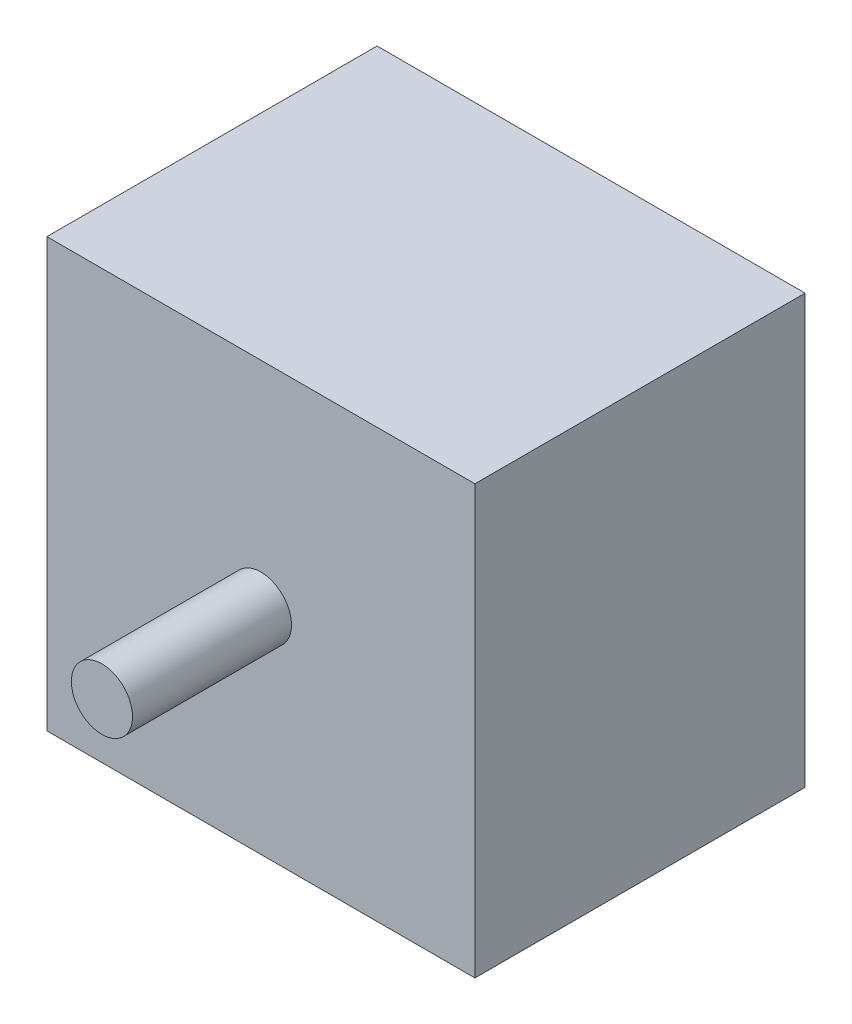
SolidWorks part; units mm, degrees
ref_plane "Front Plane" through (0, 0, 0) normal (0, 0, 1) x (1, 0, 0)
ref_plane "Top Plane" through (0, 0, 0) normal (0, 1, 0) x (1, 0, 0)
ref_plane "Right Plane" through (0, 0, 0) normal (1, 0, 0) x (0, 0, -1)
sketch "Sketch1" plane through (0, 0, 0) normal (0, 0, 1) x (1, 0, 0)
  line L0 (0, 17.5) -> (35, 17.5) construction
  line L1 (0, 0) -> (35, 0)
  line L2 (0, 0) -> (0, 35)
  line L3 (0, 35) -> (35, 35)
  line L4 (35, 0) -> (35, 35)
  line L5 (17.5, 0) -> (17.5, 35) construction
  line L6 (15.4391, 18.9151) -> (19.5609, 18.9151)
  circle A0 centre (17.5, 17.5) radius 2.5
  dimension "D3" = 5
  dimension "D1" = 35
  dimension "D2" = 35
extrude "Boss-Extrude1" add sketch "Sketch1" along normal blind 27 contours L1 L4 L3 L2 A0 | L6 A0 | L6 A0 region at (0.495, 17.5, 0) region at (17.5, 19.3583, 0) region at (17.5, 17.1462, 0)
extrude "Boss-Extrude2" add sketch "Sketch1<3>" along normal blind 40 contours L6 A0 | L6 A0 region at (17.5, 19.3583, 0) region at (17.5, 17.1462, 0)
sketch "Sketch1<3>" plane through (0, 0, 0) normal (0, 0, 1) x (1, 0, 0) same geometry as "Sketch1"
